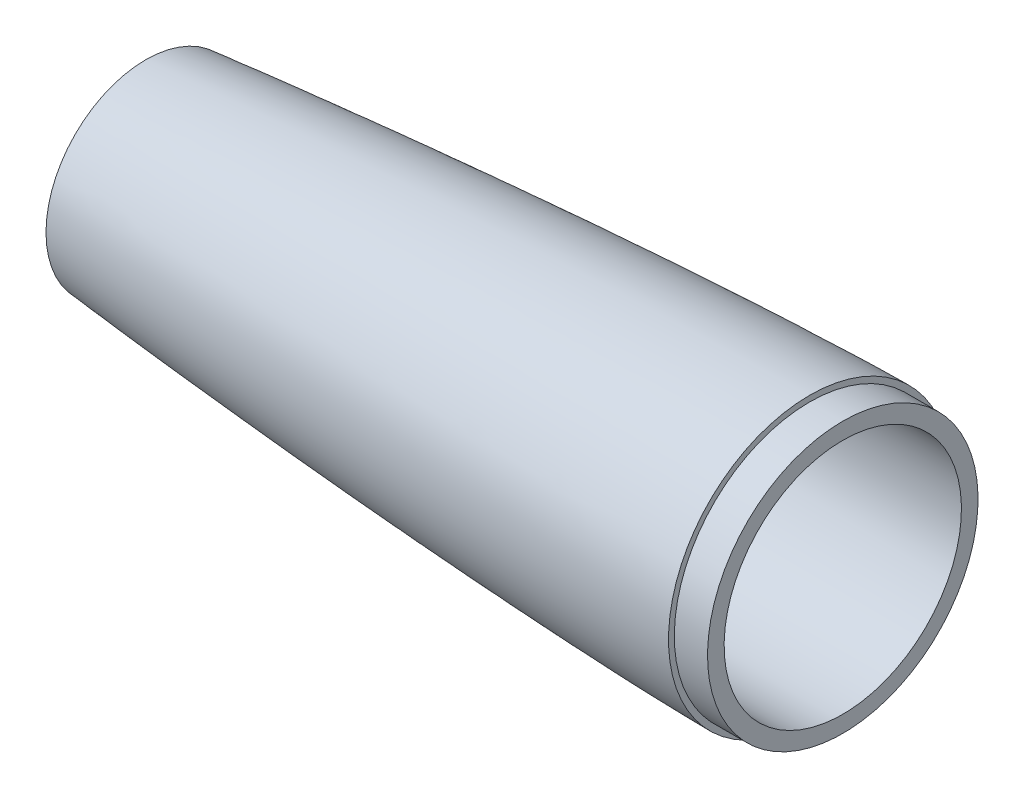
SolidWorks part; units mm, degrees
note: '?' marks a value the reader was unsure of.
other "Markup1"
sketch "Sketch5" plane through (0, 27.3, 27.3) normal (0.8928, 0.2893, 0.3454) x (0.366, -0.0189, -0.9304)
other "Markup2"
sketch "Sketch13" plane through (0, -27.3, 27.3) normal (0.8843, -0.0281, 0.466) x (0.4595, -0.1248, -0.8794)
ref_plane "Front Plane" through (0, 0, 0) normal (0, 0, 1) x (1, 0, 0)
ref_plane "Top Plane" through (0, 0, 0) normal (0, 1, 0) x (1, 0, 0)
ref_plane "Right Plane" through (0, 0, 0) normal (1, 0, 0) x (0, 0, -1)
sketch "Sketch1" plane through (0, 0, 0) normal (0, 0, 1) x (1, 0, 0)
  line L0 (0, 35.75) -> (0, 40.75)
  line L1 (0, 40.75) -> (-10, 40.75)
  line L2 (-10, 40.75) -> (-10, 42.5)
  line L3 (-393.098, 0) -> (-410, 0)
  line L4 (0, 35.75) -> (-63.8554, 35.75)
  line L7 (-63.8554, 35.75) -> (-64.0964, 40.7442) construction
  line L8 (-393.098, 0) -> (-394.217, 4.8732) construction
  arc A3 (-393.098, 0) -> (-63.8554, 35.75) centre (-10, -1994.2045) cw
  spline S0 degree 4 poles (-410, 0) (-409.9961, 0.0098) (-409.9859, 0.0279) (-409.9575, 0.0594) (-409.8982, 0.1142) (-409.8105, 0.18) (-409.6763, 0.2682) (-409.4838, 0.3796) (-409.2125, 0.5209) (-408.7822, 0.7225) (-408.0633, 1.0244) (-406.7796, 1.5019) (-404.4181, 2.2707) (-399.9785, 3.5205) (-392.2189, 5.3931) (-378.9951, 8.137) (-360.8165, 11.3764) (-338.7639, 14.8394) (-314.2234, 18.2908) (-289.6434, 21.4446) (-265.0328, 24.3509) (-240.398, 27.0419) (-215.7425, 29.5365) (-191.069, 31.8465) (-166.3795, 33.9774) (-141.6751, 35.9296) (-120.0467, 37.4773) (-101.4999, 38.6822) (-86.0388, 39.5987) (-73.6667, 40.2758) (-61.2914, 40.892) (-50.4602, 41.3719) (-41.1744, 41.7349) (-33.712, 41.9903) (-28.074, 42.1616) (-23.3482, 42.2852) (-19.5348, 42.3708) (-16.3568, 42.4293) (-13.8142, 42.4697) (-11.9071, 42.4886) (-10.6357, 42.5) (-10, 42.5) knots 0 0 0 0 0 0.000104 0.000208 0.000416 0.000802 0.001189 0.001802 0.002622 0.003838 0.005903 0.009538 0.016212 0.028478 0.051666 0.088742 0.150227 0.211711 0.273196 0.334681 0.396165 0.45765 0.519135 0.580619 0.642104 0.703588 0.765073 0.795815 0.826557 0.8573 0.888042 0.918784 0.934156 0.949527 0.962145 0.974763 0.981073 0.987382 0.993691 1 1 1 1 1 construction
  spline S1 degree 4 poles (-410, 0) (-409.9961, 0.0098) (-409.9859, 0.0279) (-409.9575, 0.0594) (-409.8982, 0.1142) (-409.8105, 0.18) (-409.6763, 0.2682) (-409.4838, 0.3796) (-409.2125, 0.5209) (-408.7822, 0.7225) (-408.0633, 1.0244) (-406.7796, 1.5019) (-404.4181, 2.2707) (-399.9785, 3.5205) (-392.2189, 5.3931) (-378.9951, 8.137) (-360.8165, 11.3764) (-338.7639, 14.8394) (-314.2234, 18.2908) (-289.6434, 21.4446) (-265.0328, 24.3509) (-240.398, 27.0419) (-215.7425, 29.5365) (-191.069, 31.8465) (-166.3795, 33.9774) (-141.6751, 35.9296) (-120.0467, 37.4773) (-101.4999, 38.6822) (-86.0388, 39.5987) (-73.6667, 40.2758) (-61.2914, 40.892) (-50.4602, 41.3719) (-41.1744, 41.7349) (-33.712, 41.9903) (-28.074, 42.1616) (-23.3482, 42.2852) (-19.5348, 42.3708) (-16.3568, 42.4293) (-13.8142, 42.4697) (-11.9071, 42.4886) (-10.6357, 42.5) (-10, 42.5) knots 0 0 0 0 0 0.000104 0.000208 0.000416 0.000802 0.001189 0.001802 0.002622 0.003838 0.005903 0.009538 0.016212 0.028478 0.051666 0.088742 0.150227 0.211711 0.273196 0.334681 0.396165 0.45765 0.519135 0.580619 0.642104 0.703588 0.765073 0.795815 0.826557 0.8573 0.888042 0.918784 0.934156 0.949527 0.962145 0.974763 0.981073 0.987382 0.993691 1 1 1 1 1
  dimension "D3" = 10
  dimension "D5" = 5
  dimension "D4" = 40.75
  dimension "D1" = 42.5
  dimension "D2" = 5
  dimension "D6" = 5
  dimension "D7" = 400
revolve "Revolve1" add sketch "Sketch1" angle 360 about L3
ref_plane "Plane1" through (-10, 0, 0) normal (1, 0, 0) x (0, 0, -1)
ref_plane "Plane2" through (-318, 0, 0) normal (1, 0, 0) x (0, 0, -1)
ref_plane "Plane3" through (-10, 0, 0) normal (1, 0, 0) x (0, 0, -1)
ref_plane "Plane4" through (-210, 0, 0) normal (1, 0, 0) x (0, 0, -1)
other "SurfaceCut1"
sketch "Sketch14" plane through (-210, 0, 0) normal (-1, 0, 0) x (0, 0, 1)
  circle A0 centre (0, 0) radius 30.052
  circle A1 centre (0, 0) radius 26.5913
  circle A2 centre (0, 0) radius 30.052 construction
  circle A3 centre (0, 0) radius 26.5913 construction
extrude "Boss-Extrude1" add sketch "Sketch14" against normal blind 30 draft 2 draft outward yes
sketch "Sketch17" plane through (0, 0, 0) normal (0, 0, 1) x (1, 0, 0)
  line L0 (-10, -42.5) -> (-10, 42.5) construction
  line L1 (-165, 0) -> (0, 0) construction
  circle A0 centre (-165, 0) radius 6
  dimension "D1" = 12
  dimension "D2" = 155
extrude "Boss-Extrude2" add sketch "Sketch17" along normal up to surface and the other way up to surface up to face at (-63.8554, 35.75, 0) other way up to face at (-63.8554, 35.75, 0)
fillet "Fillet1" radius 5 2 edges at (-159.9563, 3.2499, 30.7486) (-159.9312, 3.2105, -30.7546)
ref_axis "Axis1" through (-165, 0, -26.7787) along (0, 0, 1)?
equation "\"ConeLength\"= 400"
equation "\"D3@Sketch1\"= \"ShoulderLength\""
equation "\"ConeDiameter\"= 85"
equation "\"ShoulderLength\"= 10"
equation "\"ShoulderDiameter\"= 81.5"
equation "\"D4@Sketch1\"=\"ShoulderDiameter\"/2"
equation "\"WallThickness\"= 5"
equation "\"D5@Sketch1\"=\"WallThickness\""
equation "\"D1@Sketch1\"=\"ConeDiameter\"/2"
equation "\"ShapeParameter\"= 0"
equation "\"D2@Sketch1\"=\"WallThickness\""
equation "\"D6@Sketch1\"=\"WallThickness\""
equation "\"D7@Sketch1\"=\"ConeLength\""
